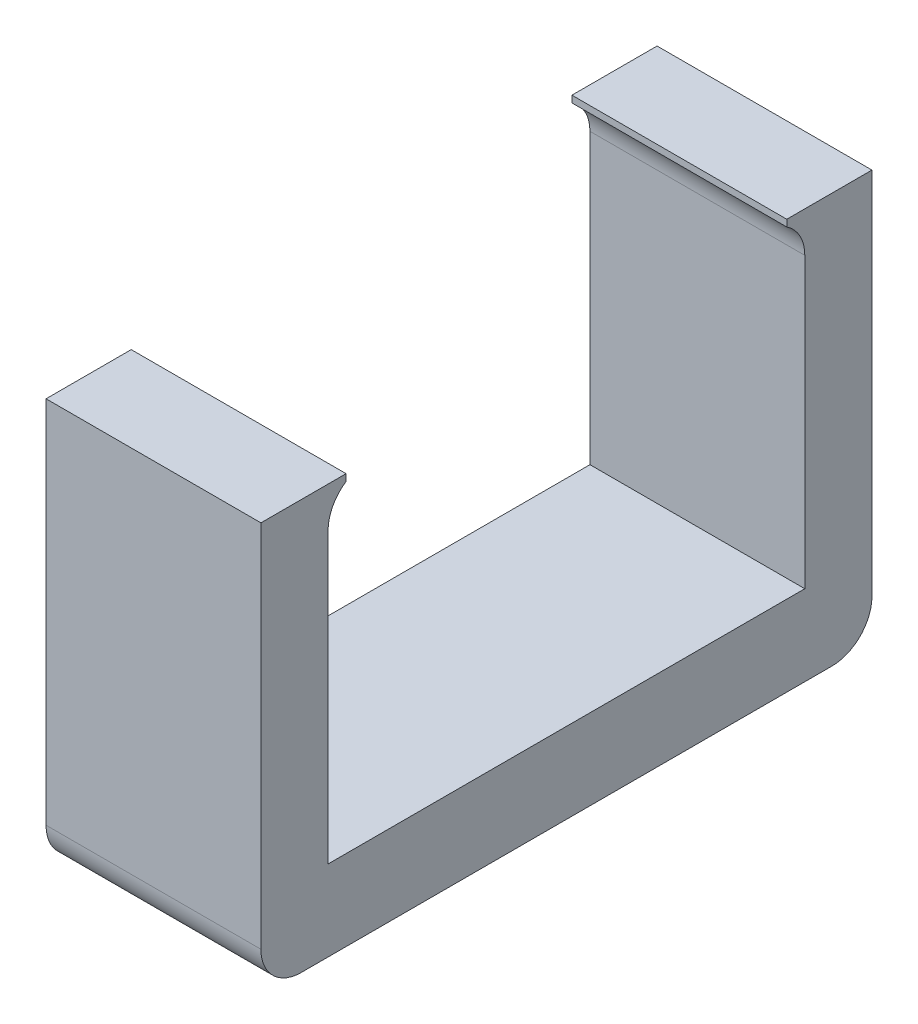
SolidWorks part; units mm, degrees
ref_plane "Front Plane" through (0, 0, 0) normal (0, 0, 1) x (1, 0, 0)
ref_plane "Top Plane" through (0, 0, 0) normal (0, 1, 0) x (1, 0, 0)
ref_plane "Right Plane" through (0, 0, 0) normal (1, 0, 0) x (0, 0, -1)
sketch "Sketch2" plane through (0, 0, 0) normal (1, 0, 0) x (0, 0, -1)
  line L0 (1.5, 0) -> (21.25, 0)
  line L1 (22.75, 1.5) -> (22.75, 15.25)
  line L2 (22.75, 15.25) -> (19.5792, 15.25)
  line L4 (20.25, 3) -> (2.5, 3)
  line L6 (3.1708, 15.25) -> (0, 15.25)
  line L7 (0, 15.25) -> (0, 1.5)
  line L8 (2.5, 3) -> (2.5, 13.75)
  line L9 (20.25, 3) -> (20.25, 13.75)
  line L10 (3.1708, 15.25) -> (3.1708, 15)
  line L11 (19.5792, 15.25) -> (19.5792, 15)
  arc A0 (21.25, 0) -> (22.75, 1.5) centre (21.25, 1.5) ccw
  arc A1 (1.5, 0) -> (0, 1.5) centre (1.5, 1.5) cw
  arc A2 (2.5, 13.75) -> (3.1708, 15) centre (4, 13.75) cw
  arc A3 (20.25, 13.75) -> (19.5792, 15) centre (18.75, 13.75) ccw
  point P11 (22.75, 0)
  point P14 (0, 0)
  dimension "D5" = 1.5
  dimension "D1" = 15.25
  dimension "D2" = 3
  dimension "D3" = 22.75
  dimension "D4" = 1.5
  dimension "D6" = 2.5
  dimension "D8" = 2.5
  dimension "D9" = 17.75
  dimension "D10" = 12.25
  dimension "D11" = 0.25
  dimension "D7" = 3.1708
extrude "ProfileBoss-Extrude1" add sketch "Sketch2" along normal blind 8
equation "\"SerratedChannelWidth\"=17.5"
equation "\"D3@Sketch2\"=\"SerratedChannelWidth\" + \"SerratedChannelChannelProngWidth\" * 2 + .25mm"
equation "\"SerratedChannelHeight\"= 12.5mm"
equation "\"D1@Sketch2\"=\"SerratedChannelHeight\" + \"SerratedChannelChannelProngWidth\" + .25mm"
equation "\"SerratedChannelBaseHeight\"= 3mm"
equation "\"D2@Sketch2\"=\"SerratedChannelBaseHeight\""
equation "\"SerratedChannelChannelProngWidth\"= 2.5mm"
equation "\"SerratedChannelLength\" = \"SerratedChannelProngClosedWidth\" + \"SerratedChannelProngOpenningWidth\""
equation "\"D1@ProfileBoss-Extrude1\"=\"SerratedChannelLength\""
equation "\"SerratedChannelProngOpenningWidth\"= 3mm"
equation "\"SerratedChannelProngBaseHeight\"= 4mm"
equation "\"SerratedChannelProngHookSize\"= 1.5mm"
equation "\"SerratedChannelProngClosedWidth\"= 5mm"
equation "\"D4@Sketch2\"=\"SerratedChannelBaseHeight\"/2"
equation "\"D6@Sketch2\"=\"SerratedChannelChannelProngWidth\""
equation "\"D8@Sketch2\"=\"SerratedChannelChannelProngWidth\""
